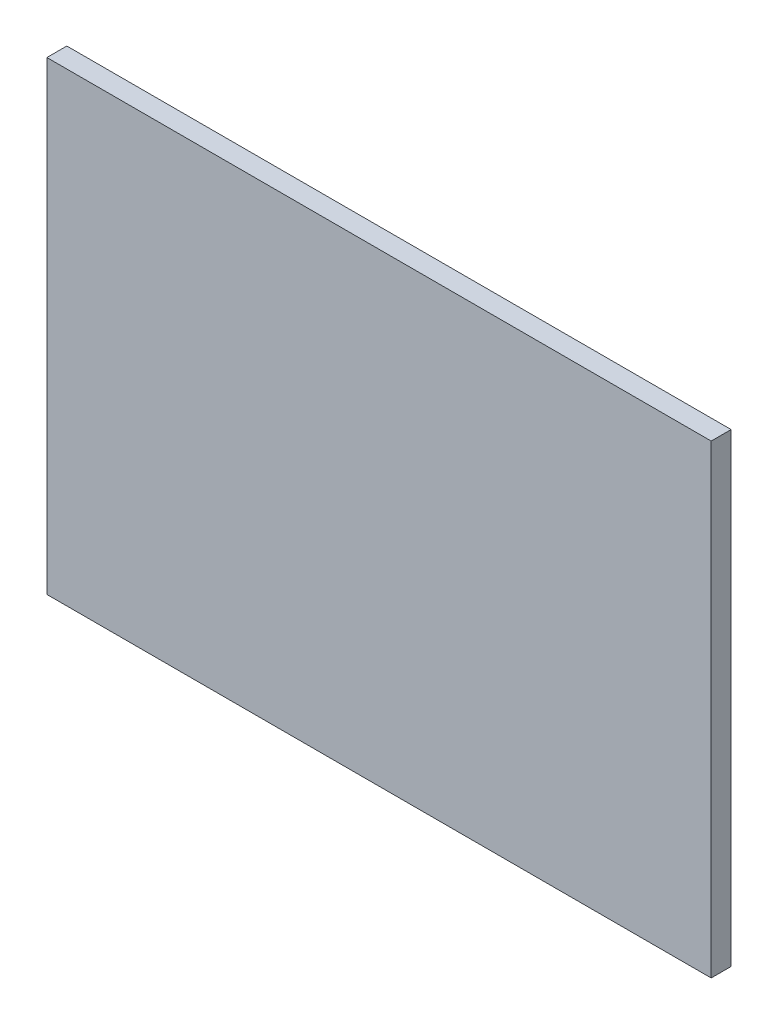
SolidWorks part; units mm, degrees
ref_plane "Front Plane" through (0, 0, 0) normal (0, 0, 1) x (1, 0, 0)
ref_plane "Top Plane" through (0, 0, 0) normal (0, 1, 0) x (1, 0, 0)
ref_plane "Right Plane" through (0, 0, 0) normal (1, 0, 0) x (0, 0, -1)
sketch "Sketch2" plane through (0, 0, 0) normal (0, 0, 1) x (1, 0, 0)
  line L1 (-50, -35) -> (50, -35)
  line L2 (-50, -35) -> (-50, 35)
  line L3 (-50, 35) -> (50, 35)
  line L4 (50, -35) -> (50, 35)
  line L5 (-50, -35) -> (50, 35) construction
  line L6 (-50, 35) -> (50, -35) construction
  point P0 (0, 0)
  dimension "D1" = 100
  dimension "D2" = 70
extrude "Boss-Extrude1" add sketch "Sketch2" along normal blind 3
